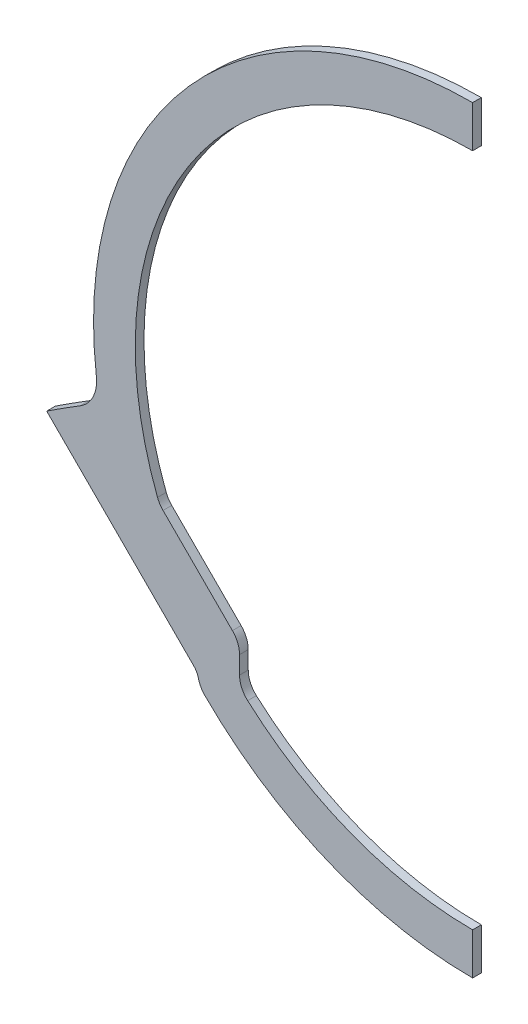
SolidWorks part; units mm, degrees
material "Balsa"
ref_plane "Front Plane" through (0, 0, 0) normal (0, 0, 1) x (1, 0, 0)
ref_plane "Top Plane" through (0, 0, 0) normal (0, 1, 0) x (1, 0, 0)
ref_plane "Right Plane" through (0, 0, 0) normal (1, 0, 0) x (0, 0, -1)
sketch "Sketch1" plane through (0, 0, 0) normal (0, 0, 1) x (1, 0, 0)
  line L0 (0, 32.094) -> (0, -346.2619) construction
  line L1 (0, 0) -> (0, 244.345) construction
  line L2 (0, 0) -> (0, 471.6969) construction
  line L3 (0, 0) -> (-283.5939, 0) construction
  line L4 (-127.2933, -32.5553) -> (-100.3525, -59.496)
  line L5 (-100.3525, -59.496) -> (-100.3525, -73.5092)
  line L6 (-100.3525, -59.496) -> (-54.3993, -105.4493) construction
  arc A0 (-54.3993, -105.4493) -> (-127.2933, -32.5553) centre (0, 21.844) ccw
  arc A2 (-100.3525, -73.5092) -> (-54.3993, -105.4493) centre (0, 21.844) ccw construction
  arc A3 (-127.2933, -32.5553) -> (-100.3525, -73.5092) centre (0, 21.844) ccw construction
  arc A4 (-100.3525, -73.5092) -> (-54.3993, -105.4493) centre (0, 21.844) ccw
  spline S2 degree 3 poles (-727.3087, -4752.7911) (287.5763, -944.0707) (320.9183, 35.1812) (49.9381, 150.9258) (45.7097, 152.4909) (37.1079, 155.2035) (32.7346, 156.3511) (27.1752, 157.5183) (26.0587, 157.7384) (23.8163, 158.1514) (22.6888, 158.3447) (19.306, 158.8811) (17.0511, 159.1813) (10.2867, 159.9126) (1.2693, 160.4377) (-7.745, 160.0789) (-14.5046, 159.4749) (-16.7575, 159.2176) (-20.1367, 158.7464) (-21.263, 158.5751) (-23.5156, 158.2037) (-24.6421, 158.0036) (-30.2426, 156.9366) (-34.6466, 155.8674) (-43.3063, 153.3113) (-47.562, 151.8242) (-55.9254, 148.4331) (-60.0331, 146.529) (-66.0807, 143.3516) (-68.0818, 142.2359) (-72.0044, 139.9197) (-73.9301, 138.7173) (-79.6017, 134.9792) (-86.884, 129.6473) (-93.6143, 123.6295) (-98.4521, 118.8554) (-100.0296, 117.2204) (-102.3424, 114.7015) (-103.1054, 113.8496) (-104.6077, 112.1297) (-105.3467, 111.2623) (-108.9818, 106.8875) (-111.6981, 103.2683) (-116.7574, 95.7975) (-119.1004, 91.9459) (-123.4121, 84.0098) (-125.3809, 79.9253) (-127.6006, 74.6695) (-128.0327, 73.61) (-128.8681, 71.4874) (-129.2719, 70.423) (-130.4422, 67.2205) (-131.1674, 65.0732) (-133.1812, 58.5951) (-135.4347, 49.861) (-136.834, 40.9354) (-137.5569, 34.168) (-137.7434, 31.9) (-137.9397, 28.4793) (-137.9911, 27.3374) (-138.0656, 25.0596) (-138.0887, 23.9223) (-138.135, 18.2442) (-137.9496, 13.7276) (-137.1441, 4.7454) (-136.5239, 0.2797) (-134.8456, -8.6005) (-133.7876, -13.015) (-131.2181, -21.791) (-129.7278, -26.0794) (-126.351, -34.4622) (-124.4643, -38.5569) (-120.2966, -46.5538) (-118.0156, -50.456) (-114.9122, -55.2108) (-114.2789, -56.1556) (-112.9868, -58.0327) (-112.3272, -58.9661) (-110.315, -61.7398) (-108.9333, -63.5482) (-104.6702, -68.8537) (-98.6716, -75.6089) (-92.0553, -81.7381) (-86.8592, -86.0978) (-85.0881, -87.5114) (-82.3719, -89.5716) (-81.4566, -90.2482) (-79.6058, -91.5811) (-78.6696, -92.238) (231.9603, -304.4561) (1345.3057, 781.0624) (3419.1463, 3416.8041) knots -1.975241 -1.975241 -1.975241 -1.975241 0.03125 0.03125 0.0625 0.0625 0.09375 0.09375 0.101563 0.101563 0.109375 0.109375 0.125 0.125 0.15625 0.1875 0.1875 0.203125 0.203125 0.210937 0.210937 0.21875 0.21875 0.25 0.25 0.28125 0.28125 0.3125 0.3125 0.328125 0.328125 0.34375 0.34375 0.375 0.40625 0.40625 0.421875 0.421875 0.429687 0.429687 0.4375 0.4375 0.46875 0.46875 0.5 0.5 0.53125 0.53125 0.539062 0.539062 0.546875 0.546875 0.5625 0.5625 0.59375 0.625 0.625 0.640625 0.640625 0.648437 0.648437 0.65625 0.65625 0.6875 0.6875 0.71875 0.71875 0.75 0.75 0.78125 0.78125 0.8125 0.8125 0.84375 0.84375 0.851562 0.851562 0.859375 0.859375 0.875 0.875 0.90625 0.9375 0.9375 0.953125 0.953125 0.960937 0.960937 0.96875 0.96875 3.533217 3.533217 3.533217 3.533217 only from (66.3397, 143.1887) to (-66.0465, -100.0388)
  spline S3 degree 3 poles (66.3397, 143.1887) (62.3323, 145.3909) (58.2494, 147.3758) (49.9381, 150.9258) (45.7097, 152.4909) (37.1079, 155.2035) (32.7346, 156.3511) (27.1752, 157.5183) (26.0587, 157.7384) (23.8163, 158.1514) (22.6888, 158.3447) (19.306, 158.8811) (17.0511, 159.1813) (10.2867, 159.9126) (1.2693, 160.4377) (-7.745, 160.0789) (-14.5046, 159.4749) (-16.7575, 159.2176) (-20.1367, 158.7464) (-21.263, 158.5751) (-23.5156, 158.2037) (-24.6421, 158.0036) (-30.2426, 156.9366) (-34.6466, 155.8674) (-43.3063, 153.3113) (-47.562, 151.8242) (-55.9254, 148.4331) (-60.0331, 146.529) (-66.0807, 143.3516) (-68.0818, 142.2359) (-72.0044, 139.9197) (-73.9301, 138.7173) (-79.6017, 134.9792) (-86.884, 129.6473) (-93.6143, 123.6295) (-98.4521, 118.8554) (-100.0296, 117.2204) (-102.3424, 114.7015) (-103.1054, 113.8496) (-104.6077, 112.1297) (-105.3467, 111.2623) (-108.9818, 106.8875) (-111.6981, 103.2683) (-116.7574, 95.7975) (-119.1004, 91.9459) (-123.4121, 84.0098) (-125.3809, 79.9253) (-127.6006, 74.6695) (-128.0327, 73.61) (-128.8681, 71.4874) (-129.2719, 70.423) (-130.4422, 67.2205) (-131.1674, 65.0732) (-133.1812, 58.5951) (-135.4347, 49.861) (-136.834, 40.9354) (-137.5569, 34.168) (-137.7434, 31.9) (-137.9397, 28.4793) (-137.9911, 27.3374) (-138.0656, 25.0596) (-138.0887, 23.9223) (-138.135, 18.2442) (-137.9496, 13.7276) (-137.1441, 4.7454) (-136.5239, 0.2797) (-134.8456, -8.6005) (-133.7876, -13.015) (-131.2181, -21.791) (-129.7278, -26.0794) (-127.6847, -31.1513) (-127.3213, -32.0275) (-126.9491, -32.8995) knots 0 0 0 0 0.03125 0.03125 0.0625 0.0625 0.09375 0.09375 0.101563 0.101563 0.109375 0.109375 0.125 0.125 0.15625 0.1875 0.1875 0.203125 0.203125 0.210937 0.210937 0.21875 0.21875 0.25 0.25 0.28125 0.28125 0.3125 0.3125 0.328125 0.328125 0.34375 0.34375 0.375 0.40625 0.40625 0.421875 0.421875 0.429687 0.429687 0.4375 0.4375 0.46875 0.46875 0.5 0.5 0.53125 0.53125 0.539062 0.539062 0.546875 0.546875 0.5625 0.5625 0.59375 0.625 0.625 0.640625 0.640625 0.648437 0.648437 0.65625 0.65625 0.6875 0.6875 0.71875 0.71875 0.75 0.75 0.78125 0.78125 0.787815 0.787815 0.787815 0.787815 construction
  point P2 (0, 160.2226)
  point P3 (0, -116.9127)
  point P23 (-100.3525, -59.496)
  dimension "D1" = 277.1353
  dimension "D2" = 276.86
  dimension "D3" = 21.844
  dimension "D5" = 45
  dimension "D6" = 113.03
  dimension "D4" = 38.1
  dimension "D7" = 45
extrude "Boss-Extrude1" add sketch "Sketch1" along normal mid plane 3.175
sketch "Sketch2" plane through (0, 0, 1.5875) normal (0, 0, 1) x (1, 0, 0)
  line L2 (-114.3729, -23.9231) -> (-85.1125, -53.1834)
  line L3 (-114.3729, -23.9231) -> (-85.1125, -53.1834)
  line L4 (-85.1125, -53.1834) -> (-85.1125, -67.2157)
  line L5 (-85.1125, -53.1834) -> (-85.1125, -67.2157)
  arc A2 (-85.1125, -67.2157) -> (-114.3729, -23.9231) centre (0, 21.844) ccw
  arc A3 (-85.1125, -67.2157) -> (-114.3729, -23.9231) centre (0, 21.844) ccw
  dimension "D1" = 15.24
extrude "Cut-Extrude1" cut sketch "Sketch2" against normal up to surface (3.175 mm away) up to face at (-32.8418, -4.8687, -1.5875)
fillet "Fillet1" radius 8.89 6 edges at (-127.2933, -32.5553, 0) (-114.3729, -23.9231, 0) (-100.3525, -59.496, 0) (-100.3525, -73.5092, 0) (-85.1125, -53.1834, 0) (-85.1125, -67.2157, 0)
sketch "Sketch3" plane through (0, 0, 1.5875) normal (0, 0, 1) x (1, 0, 0)
  line L0 (-0.0002, 49.9919) -> (-0.0176, 733.2) construction
  line L1 (-0.0002, 49.9919) -> (-0.0176, 733.2) construction
  line L2 (-136.2041, -28.3557) -> (-0.0002, 49.9919) construction
  line L3 (136.2076, -28.3488) -> (-0.0002, 49.9919) construction
  line L4 (-136.2041, -28.3557) -> (-0.0002, 49.9919) construction
  line L5 (136.2076, -28.3488) -> (-0.0002, 49.9919) construction
  line L6 (-1.6539, 152.6441) -> (-1.654, 160.2641)
  line L7 (1.6481, 152.6442) -> (1.648, 160.2642)
  line L8 (-1.6539, 152.6441) -> (1.6481, 152.6442)
  line L9 (119.8485, -45.962) -> (106.7537, -38.3747)
  line L10 (121.4435, -43.2066) -> (108.3479, -35.6188)
  line L18 (121.4435, -43.2066) -> (108.3479, -35.6188)
  line L30 (-123.167, -47.8929) -> (-104.8722, -37.2914)
  line L35 (119.8485, -45.962) -> (106.7537, -38.3747)
  line L47 (108.5244, -35.721) -> (120.1169, -46.1175) construction
  line L48 (114.3206, -40.9193) -> (126.5619, -48.0121) construction
  line L49 (113.8577, -42.5592) -> (122.0137, -47.2849)
  line L50 (115.5132, -39.7021) -> (123.6691, -44.4278)
  line L51 (113.8577, -42.5592) -> (115.5132, -39.7021)
  line L52 (122.0137, -47.2849) -> (123.6691, -44.4278)
  line L58 (-124.7703, -45.1423) -> (-106.4681, -34.5364)
  line L59 (-124.7703, -45.1423) -> (-123.167, -47.8929)
  line L71 (-124.7703, -45.1423) -> (-123.167, -47.8929) construction
  line L72 (-124.7703, -45.1423) -> (-106.4681, -34.5364) construction
  line L73 (-123.167, -47.8929) -> (-104.8722, -37.2914) construction
  line L74 (-123.167, -47.8929) -> (-107.9499, -35.3951) construction
  line L75 (-115.5584, -41.644) -> (-110.9064, -38.9482) construction
  line L76 (-119.3826, -41.9518) -> (-112.6266, -38.0369)
  line L77 (-117.727, -44.8088) -> (-110.971, -40.8938)
  line L78 (-119.3826, -41.9518) -> (-117.727, -44.8088)
  line L79 (-112.6266, -38.0369) -> (-110.971, -40.8938)
  arc A0 (-54.3993, -105.4493) -> (-127.2933, -32.5553) centre (0, 21.844) ccw construction
  arc A2 (-1.654, 160.2641) -> (-130.2816, -24.9489) centre (0, 21.844) ccw construction
  arc A3 (-130.2816, -24.9489) -> (-127.2933, -32.5553) centre (0, 21.844) ccw construction
  arc A4 (-1.654, 160.2641) -> (-130.2816, -24.9489) centre (0, 21.844) ccw construction
  arc A5 (-130.2816, -24.9489) -> (-127.9919, -30.8906) centre (0, 21.844) ccw construction
  arc A14 (130.2841, -24.9419) -> (1.648, 160.2642) centre (0, 21.844) ccw construction
  arc A15 (1.648, 160.2642) -> (-1.654, 160.2641) centre (0, 21.844) ccw
  arc A16 (130.2841, -24.9419) -> (1.648, 160.2642) centre (0, 21.844) ccw construction
  arc A17 (1.648, 160.2642) -> (-1.654, 160.2641) centre (0, 21.844) ccw
  spline S0 degree 3 poles (106.7537, -38.3747) (107.2851, -37.456) (107.8165, -36.5374) (108.3479, -35.6188) knots 0 0 0 0 1 1 1 1 weights 1 1 1 1
  spline S1 degree 3 poles (119.8485, -45.962) (120.3802, -45.0435) (120.9118, -44.1251) (121.4435, -43.2066) knots 0 0 0 0 1 1 1 1 weights 1 1 1 1
  spline S2 degree 3 poles (-2881.8279, -5110.8457) (-867.0486, -1792.2476) (1150.0458, 1692.4969) (3017.7739, 5081.3636) knots -1883.036326 -1883.036326 -1883.036326 -1883.036326 1886.727416 1886.727416 1886.727416 1886.727416 weights 1.019131 0.993605 0.993623 1.019186 only from (119.8485, -45.962) to (121.4435, -43.2066)
  spline S3 degree 3 poles (-3036.589, 5119.5324) (-1127.1857, 1694.954) (886.2714, -1780.7488) (2908.8083, -5143.6151) knots -1884.72297 -1884.72297 -1884.72297 -1884.72297 1885.121052 1885.121052 1885.121052 1885.121052 weights 1.011938 0.996023 0.996021 1.01193 only from (-106.4681, -34.5364) to (-104.8722, -37.2914)
  spline S4 degree 3 poles (-106.4681, -34.5364) (-105.9361, -35.4547) (-105.4042, -36.373) (-104.8722, -37.2914) knots 0 0 0 0 1 1 1 1 weights 1 1 1 1 construction
  spline S6 degree 3 poles (-2896.3363, -5115.1565) (-877.9448, -1779.9949) (1136.8197, 1703.1959) (3011.0409, 5097.7049) knots -1882.139818 -1882.139818 -1882.139818 -1882.139818 1887.64982 1887.64982 1887.64982 1887.64982 weights 1.017241 0.994226 0.994252 1.017325 only from (106.7537, -38.3747) to (108.3479, -35.6188)
  point P49 (-116.0256, -43.8229)
  point P50 (120.451, -46.3794)
  arc M19 (-97.7394, -76.186) -> (-127.9919, -30.8906) centre (0, 21.844) ccw
  line M21 (-126.0584, -33.7901) -> (-102.9564, -56.8922)
  dimension "D1" = 3.302
  dimension "D2" = 7.62
  dimension "D4" = 3.302
  dimension "D5" = 7.62
  dimension "D6" = 3.302
  dimension "D7" = 5.842
extrude "Cut-Extrude2" [suppressed] cut sketch "Sketch3" against normal through all contours L79 L76 L77 M21 | L6 L8 L7 M19 | L51 L49 L50 M19
sketch "Sketch4" plane through (0, 0, 0) normal (1, 0, 0) x (0, 0, -1)
  line L1 (-96.2805, 232.7957) -> (122.2438, 232.7957)
  line L2 (-96.2805, 232.7957) -> (-96.2805, -207.8589)
  line L3 (-96.2805, -207.8589) -> (122.2438, -207.8589)
  line L4 (122.2438, 232.7957) -> (122.2438, -207.8589)
extrude "Cut-Extrude3" cut sketch "Sketch4" along normal through all
sketch "Sketch5" plane through (0, 0, 0) normal (0, 0, 1) x (1, 0, 0)
  line L0 (0, 0) -> (-220.3195, 0) construction
  line L3 (-100.3441, -70.2779) -> (-93.132, -63.0671)
  line L4 (-100.3441, -70.2779) -> (-155.5427, -15.0686)
  line L5 (-93.132, -63.0671) -> (-135.3862, -2.54)
  arc A0 (-100.3525, -69.8905) -> (-97.7394, -76.186) centre (-91.4625, -69.8905) ccw construction
  arc A1 (-135.3862, -2.54) -> (-155.5427, -15.0686) centre (85.5484, -380.4649) ccw
  dimension "D3" = 437.7663
  dimension "D1" = 120.65
  dimension "D2" = 45.006
  dimension "D4" = 135.3862
  dimension "D5" = 2.54
  dimension "D6" = 15.0686
extrude "Boss-Extrude2" add sketch "Sketch5" along normal mid plane 3.175
fillet "Fillet2" radius 12.7 1 edges at (-136.1813, -3.0059, 0)
fillet "Fillet3" radius 6.35 1 edges at (-100.3441, -70.2779, 0)
equation "\"a\"= 0.06"
equation "\"slotwidth\"=0.13"
equation "\"slotheight\"=0.3"
